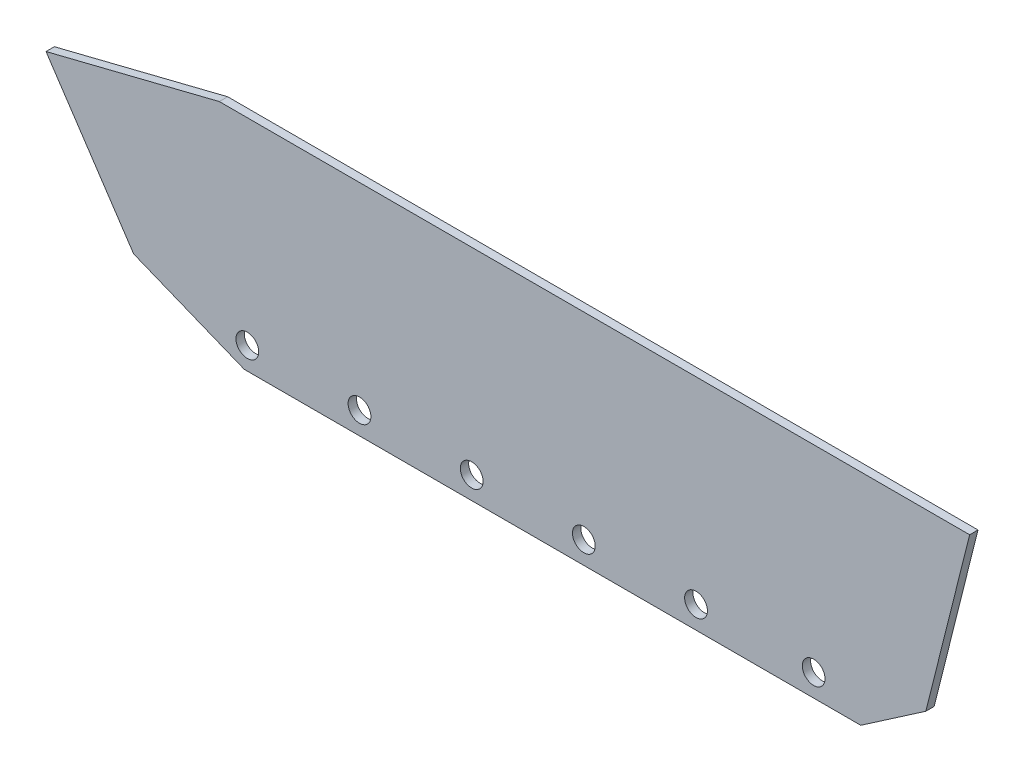
SolidWorks part; units mm, degrees
material "5052-H32"
ref_plane "Front Plane" through (0, 0, 0) normal (0, 0, 1) x (1, 0, 0)
ref_plane "Top Plane" through (0, 0, 0) normal (0, 1, 0) x (1, 0, 0)
ref_plane "Right Plane" through (0, 0, 0) normal (1, 0, 0) x (0, 0, -1)
sketch "Sketch1" plane through (0, 0, 0) normal (0, 0, 1) x (1, 0, 0)
  line L1 (428.1206, 33.3333) -> (428.1206, 28.5708)
  line L3 (428.1206, 28.5708) -> (0, 28.5708)
  line L4 (0, 28.5708) -> (-98.8794, 3.851)
  line L6 (-98.8794, 3.851) -> (-31.8794, -96.649)
  line L7 (428.1206, 28.5708) -> (403.1206, -71.149)
  line L9 (403.1206, -71.149) -> (366, -96.649)
  line L10 (-31.8794, -96.649) -> (366, -96.649)
  circle A0 centre (16, -83.899) radius 6.5
  circle A1 centre (80, -83.899) radius 6.5
  circle A2 centre (144, -83.899) radius 6.5
  circle A3 centre (208, -83.899) radius 6.5
  circle A4 centre (272, -83.899) radius 6.5
  circle A5 centre (339.1206, -83.899) radius 6.5
  point P0 (-48.8794, -71.149)
  point P2 (-31.8794, -96.649)
  point P8 (48, -83.899)
  point P9 (403.1206, -71.149)
  dimension "D2" = 32
  dimension "D4" = 64
  dimension "D1" = 25.5
  dimension "D3" = 75
  dimension "D5" = 25
  dimension "D6" = 64
  dimension "D7" = 527
  dimension "D9" = 64
  dimension "D10" = 64
  dimension "D11" = 64
  dimension "D12" = 123.69
  dimension "D13" = 12.75
extrude "Boss-Extrude1" add sketch "Sketch1" along normal blind 4.7625 contours L3 L4 L6 L10 L9 L7
extrude "Cut-Extrude1" cut sketch "Sketch1<4>" along normal through all contours A0 | A1 | A2 | A3 | A4 | A5 region at (16, -83.899, 0)
sketch "Sketch1<4>" plane through (0, 0, 0) normal (0, 0, 1) x (1, 0, 0) same geometry as "Sketch1"
sketch "Sketch2" plane through (0, 0, 0) normal (0, 0, -1) x (-1, 0, 0)
  circle A0 centre (-307.1206, -83.899) radius 6.5
  circle A2 centre (-249.5603, -111.8778) radius 6.5
  circle A3 centre (-192, -83.899) radius 6.5
  circle A4 centre (-128, -83.899) radius 6.5
  circle A5 centre (-64, -83.899) radius 6.5
  circle A6 centre (0, -83.899) radius 6.5
  dimension "D2" = 0
  dimension "D3" = 64
  dimension "D4" = 64
  dimension "D5" = 64
  dimension "D6" = 64
  dimension "D7" = 64
  dimension "D1" = 32
sketch "Sketch5" plane through (0, 0, 0) normal (0, 0, -1) x (-1, 0, 0)
  line L0 (48.8794, -71.149) -> (-14.2353, -96.649)
  line L1 (31.8794, -96.649) -> (-366, -96.649) construction
  line L2 (-14.2353, -96.649) -> (31.8794, -96.649)
  line L3 (31.8794, -96.649) -> (48.8794, -71.149)
  line L6 (-366, -96.649) -> (-403.1206, -71.149)
  line L7 (-403.1206, -71.149) -> (-352, -71.149)
  line L9 (-352, -71.149) -> (-326.5, -96.649)
  line L11 (-366, -96.649) -> (-326.5, -96.649)
  dimension "D1" = 22
  dimension "D2" = 45
extrude "Cut-Extrude2" [suppressed] cut sketch "Sketch5" against normal up to next
sketch "Sketch6" plane through (0, 0, 4.7625) normal (0, 0, 1) x (1, 0, 0)
  line L0 (-48.8794, -71.149) -> (14.2353, -96.649)
  line L1 (-31.8794, -96.649) -> (366, -96.649) construction
  line L2 (14.2353, -96.649) -> (-31.8794, -96.649)
  line L3 (-31.8794, -96.649) -> (-48.8794, -71.149)
  dimension "D1" = 158
extrude "Cut-Extrude3" cut sketch "Sketch6" against normal blind 10
